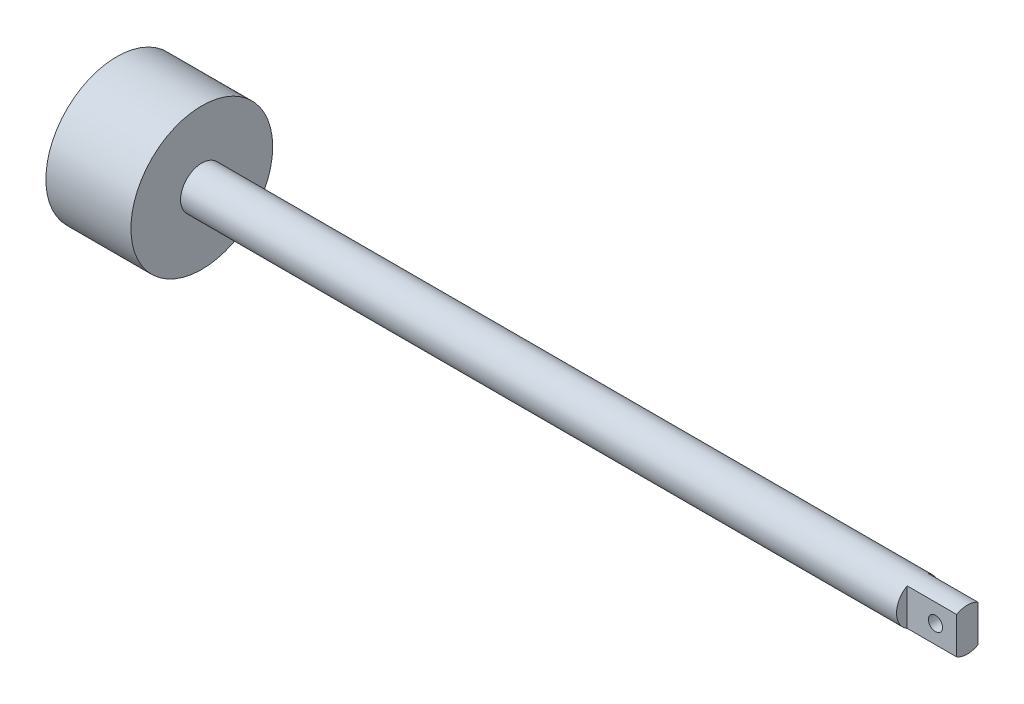
SolidWorks part; units mm, degrees
material "6061 Alloy"
ref_plane "Front Plane" through (0, 0, 0) normal (0, 0, 1) x (1, 0, 0)
ref_plane "Top Plane" through (0, 0, 0) normal (0, 1, 0) x (1, 0, 0)
ref_plane "Right Plane" through (0, 0, 0) normal (1, 0, 0) x (0, 0, -1)
sketch "Sketch1" plane through (0, 0, 0) normal (1, 0, 0) x (0, 0, -1)
  circle A0 centre (0, 0) radius 50
  circle A1 centre (0, 0) radius 15
  dimension "D1" = 100
  dimension "D2" = 30
extrude "Boss-Extrude2" add sketch "Sketch1" along normal blind 60 contours A1 | A0 A1 region at (0, 0, 48.5858) region at (0, 0, 0)
extrude "Boss-Extrude3" add sketch "Sketch1<3>" along normal blind 600 contours A1 region at (0, 0, 0)
sketch "Sketch1<3>" plane through (0, 0, 0) normal (1, 0, 0) x (0, 0, -1) same geometry as "Sketch1"
sketch "Sketch2" plane through (0, 0, 0) normal (0, 1, 0) x (1, 0, 0)
  line L1 (600, -15) -> (600, 15) construction
  line L2 (600, 7.5) -> (565, 7.5)
  line L4 (565, -7.5) -> (600, -7.5)
  line L5 (600, 7.5) -> (600, 15)
  line L6 (600, 15) -> (565, 15)
  line L7 (600, 15) -> (60, 15) construction
  line L8 (565, 15) -> (565, 7.5)
  line L9 (565, -7.5) -> (565, -15)
  line L10 (60, -15) -> (600, -15) construction
  line L11 (565, -15) -> (600, -15)
  line L12 (600, -15) -> (600, -7.5)
  dimension "D1" = 15
  dimension "D2" = 35
  dimension "D3" = 35
  dimension "D5" = 7.5
extrude "Cut-Extrude1" cut sketch "Sketch2" against normal up to next and the other way up to next contours L4 L2 | L6 L8 L2 L5 | L11 L12 L4 L9 region at (582.5, 0, -11.25) region at (582.5, 0, 11.25)
sketch "Sketch3" plane through (0, 0, 0) normal (0, 0, 1) x (1, 0, 0)
  line L0 (585, 0) -> (600, 0) construction
  line L2 (600, 12.9904) -> (600, -12.9904) construction
  circle A0 centre (585, 0) radius 5
  dimension "D2" = 10
  dimension "D1" = 15
extrude "Cut-Extrude2" cut sketch "Sketch3" against normal up to next and the other way up to next contours A0 region at (585, 0, 0)
